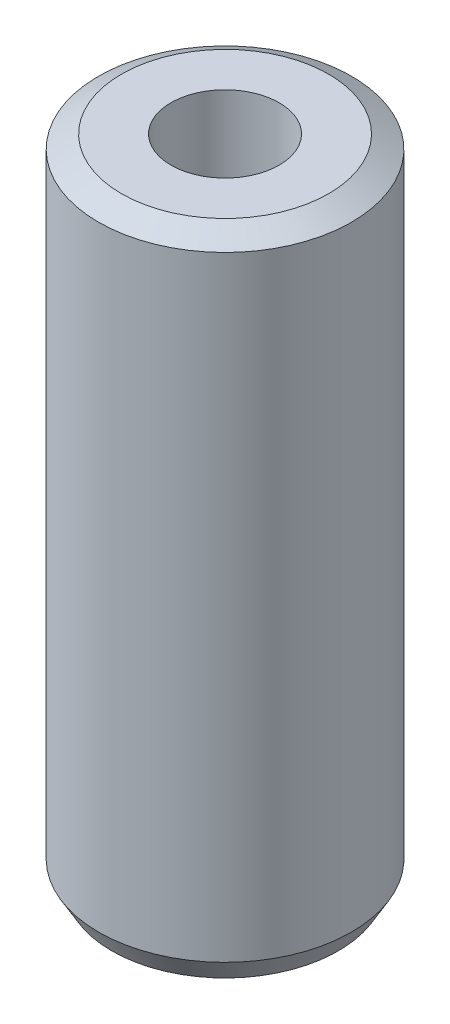
SolidWorks part; units mm, degrees
ref_plane "Front Plane" through (0, 0, 0) normal (0, 0, 1) x (1, 0, 0)
ref_plane "Top Plane" through (0, 0, 0) normal (0, 1, 0) x (1, 0, 0)
ref_plane "Right Plane" through (0, 0, 0) normal (1, 0, 0) x (0, 0, -1)
sketch "Sketch1" plane through (0, 0, 0) normal (0, 1, 0) x (1, 0, 0)
  circle A0 centre (0, 0) radius 45
  dimension "SHAFT_OD" = 90
extrude "Boss-Extrude1" add sketch "Sketch1" along normal blind 231.5837
sketch "Sketch2" plane through (0, 0, 0) normal (0, 1, 0) x (1, 0, 0)
  circle A0 centre (0, 0) radius 19.2531
  dimension "BORE_D" = 38.5063
extrude "Cut-Extrude1" cut sketch "Sketch2" along normal through all
chamfer "Chamfer1" distance 4.7053 angle 60 2 edges at (0, 231.5837, 45) (0, 0, 45) first distance on face at (0, 231.5837, 45) first distance on face at (0, 0, 19.2531)
